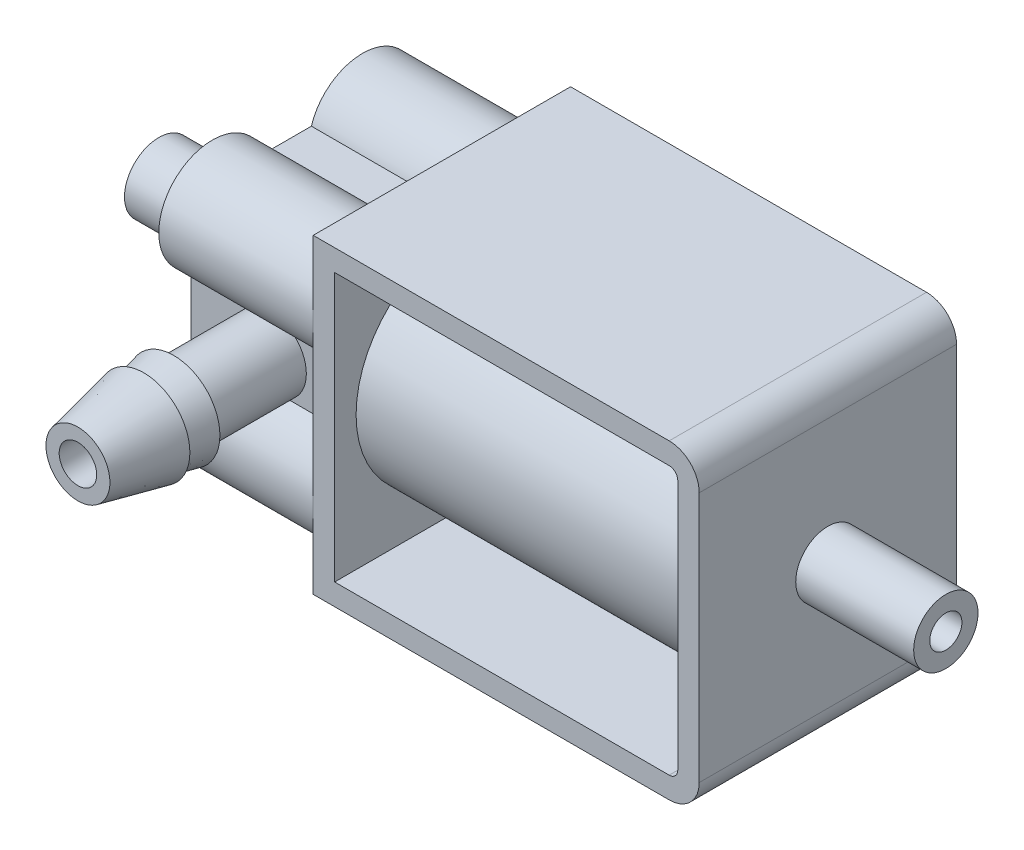
SolidWorks part; units mm, degrees
note: The reader was unsure of these and kept them because the rebuilt part matched: shared geometry of "Sketch4<6>".
ref_plane "Front Plane" through (0, 0, 0) normal (0, 0, 1) x (1, 0, 0)
ref_plane "Top Plane" through (0, 0, 0) normal (0, 1, 0) x (1, 0, 0)
ref_plane "Right Plane" through (0, 0, 0) normal (1, 0, 0) x (0, 0, -1)
sketch "Sketch1" plane through (0, 0, 0) normal (0, 0, 1) x (1, 0, 0)
  line L0 (9, -5.85) -> (9, 5.85)
  line L1 (-8, -6.25) -> (7.6, -6.25)
  line L2 (-8, -6.25) -> (-8, 6.25)
  line L3 (-8, 6.25) -> (7.6, 6.25)
  line L4 (8, -5.85) -> (8, 5.85)
  line L5 (-8, -6.25) -> (8, 6.25) construction
  line L6 (-8, 6.25) -> (8, -6.25) construction
  line L7 (-9, 7.25) -> (7.6, 7.25)
  line L8 (-9, -7.25) -> (-9, 7.25)
  line L9 (-9, -7.25) -> (7.6, -7.25)
  arc A0 (7.6, -6.25) -> (8, -5.85) centre (7.6, -5.85) ccw
  arc A1 (7.6, 6.25) -> (8, 5.85) centre (7.6, 5.85) cw
  arc A2 (7.6, 7.25) -> (9, 5.85) centre (7.6, 5.85) cw
  arc A3 (7.6, -7.25) -> (9, -5.85) centre (7.6, -5.85) ccw
  point P0 (0, 0)
  dimension "D3" = 0.4
  dimension "D1" = 18
  dimension "D2" = 14.5
  dimension "D4" = 1
extrude "Boss-Extrude1" add sketch "Sketch1" along normal blind 12
sketch "Sketch2" plane through (9, 0, 0) normal (1, 0, 0) x (0, 0, -1)
  line L0 (-12, -5.85) -> (0, 5.85) construction
  line L1 (-12, 5.85) -> (0, -5.85) construction
  line L2 (0, -5.85) -> (0, 5.85) construction
  circle A0 centre (-6, 0) radius 1.5
  circle A1 centre (-6, 0) radius 0.75
  point P12 (-6, 0)
  point P13 (0, 0)
  dimension "D1" = 3
  dimension "D2" = 1.5
extrude "Boss-Extrude2" add sketch "Sketch2" along normal blind 5.5
sketch "Sketch3" plane through (-8, 0, 0) normal (1, 0, 0) x (0, 0, -1)
  line L0 (-12, -6.25) -> (0, 6.25) construction
  line L1 (-12, 6.25) -> (0, -6.25) construction
  circle A0 centre (-6, 0) radius 5
  point P10 (-6, 0)
  point P11 (0, 0)
  dimension "D1" = 10
extrude "Boss-Extrude3" add sketch "Sketch3" along normal up to next
sketch "Sketch4" plane through (-9, 0, 0) normal (-1, 0, 0) x (0, 0, 1)
  line L0 (2.5, -3.75) -> (9.5, -3.75) construction
  line L1 (2.5, -3.75) -> (2.5, 3.75) construction
  line L2 (2.5, -3.75) -> (9.5, 3.75) construction
  line L3 (2.5, 3.75) -> (9.5, -3.75) construction
  line L4 (0, 7.25) -> (12, -7.25) construction
  line L5 (12, 7.25) -> (0, -7.25) construction
  line L6 (2.5, 3.75) -> (9.5, 3.75) construction
  line L7 (1.5, -4.5) -> (10.5, -4.5)
  line L8 (1.5, -4.5) -> (1.5, 4.5)
  line L9 (1.5, 4.5) -> (10.5, 4.5)
  line L10 (10.5, -4.5) -> (10.5, 4.5)
  line L11 (1.5, -4.5) -> (10.5, 4.5) construction
  line L12 (1.5, 4.5) -> (10.5, -4.5) construction
  line L13 (2.5, 3.75) -> (9.5, 3.75) construction
  circle A0 centre (2.5, -3.75) radius 2.5
  circle A1 centre (9.5, -3.75) radius 2.5
  circle A2 centre (9.5, 3.75) radius 2.5
  circle A3 centre (2.5, 3.75) radius 2.5
  circle A4 centre (2.5, 3.75) radius 1.85
  circle A5 centre (9.5, 3.75) radius 1.85
  circle A6 centre (9.5, -3.75) radius 1.85
  circle A7 centre (2.5, -3.75) radius 1.85
  circle A8 centre (2.5, 3.75) radius 1.1
  circle A9 centre (9.5, 3.75) radius 1.1
  circle A10 centre (9.5, -3.75) radius 1.1
  circle A11 centre (2.5, -3.75) radius 1.1
  point P2 (6, 0)
  point P4 (2.5, -3.75)
  point P20 (6, 0)
  point P21 (6, 0)
  dimension "D1" = 5
  dimension "D7" = 3.7
  dimension "D11" = 2.2
  dimension "D4" = 7
  dimension "D5" = 7.5
  dimension "D6" = 9
  dimension "D10" = 7
  dimension "D14" = 7
  dimension "D2" = 2
  dimension "D3" = 2
  dimension "D8" = 2
  dimension "D9" = 2
  dimension "D12" = 2
  dimension "D13" = 2
extrude "Boss-Extrude4" add sketch "Sketch4" along normal blind 7.2 separate body contours A5 L10 A2 L9 | L10 A5 L9 | L9 A5 L10 | A3 L8 A0 L7 A1 L10 A2 L9 | A4 L8 A3 L9 | A4 L9 A3 L8 | A7 L7 A0 L8 | A7 L8 A0 L7 | A6 L7 A1 L10 | A6 L10 A1 L7 | A5 L9 A2 L10
extrude "Boss-Extrude6" add sketch "Sketch4<6>" along normal blind 3.7 separate body contours A11 L7 A7 L8 | A11 L8 A7 L7 | A11 L8 L7 | A10 L7 A6 L10 | A10 L10 A6 L7 | A10 L7 L10 | A9 L9 L10 A5 | A9 L10 L9 | A9 L9 A5 L10 | A8 L8 A4 L9 | A8 L9 A4 L8 | A8 L9 L8
sketch "Sketch4<6>" plane through (-9, 0, 0) normal (-1, 0, 0) x (0, 0, 1) same geometry as "Sketch4"
combine bodies "Combine1" operation type add bodies to combine 104 106 109 108 107
sketch "Sketch5" plane through (-16.2, 0, 0) normal (-1, 0, 0) x (0, 0, 1)
  line L0 (6, 4.5) -> (6, -4.5) construction
  line L1 (4.8848, 4.5) -> (7.1152, 4.5) construction
  line L2 (4.8848, -4.5) -> (7.1152, -4.5) construction
  circle A0 centre (6, 0) radius 1.6
  circle A1 centre (6, 0) radius 0.57
  dimension "D1" = 3.2
  dimension "D2" = 1.14
extrude "Boss-Extrude7" add sketch "Sketch5" along normal blind 6
ref_plane "Plane1" through (0, 0, 15) normal (0, 0, 1) x (1, 0, 0)
sketch "Sketch6" plane through (0, 0, 15) normal (0, 0, 1) x (1, 0, 0)
  line L0 (-9, 1.4587) -> (-9, 6.25) construction
  line L1 (-16.2, -1.4587) -> (-9, -1.4587) construction
  line L2 (-16.2, 1.4587) -> (-9, 1.4587) construction
  line L3 (-16.2, -1.4587) -> (-9, -1.4587)
  line L4 (-16.2, 1.4587) -> (-9, 1.4587)
  line L5 (-12.5, 1.4587) -> (-12.5, -1.4587)
  circle A0 centre (-12.5, 0) radius 1.68
  circle A1 centre (-12.5, 0) radius 0.875
  point P11 (-12.5, 0.2784)
  dimension "D2" = 3.36
  dimension "D3" = 1.75
  dimension "D1" = 3.5
extrude "Boss-Extrude8" add sketch "Sketch6" against normal up to next contours A1 L5 L3 A0 L4 | A1 L5 L4 A0 L3 | L4 A0 | L3 A0
ref_plane "Plane2" through (-12.5, 0, 0) normal (-1, 0, 0) x (0, 0, 1)
sketch "Sketch8" plane through (-12.5, 0, 0) normal (-1, 0, 0) x (0, 0, 1)
  line L0 (15, -1.68) -> (15, 1.68) construction
  line L1 (15, -1.68) -> (15, 1.68)
  line L2 (15, 1.68) -> (15, 2.15)
  line L3 (15, 2.15) -> (16.4, 1.85)
  line L4 (15, 0) -> (19.47, 0) construction
  line L5 (16.4, 1.85) -> (16.4, 2.15)
  line L6 (16.4, 2.15) -> (19.47, 1.4921)
  line L7 (19.47, 1.4921) -> (19.47, 0)
  line L8 (19.47, 0.875) -> (15, 0.875)
  point P2 (15, 0)
  dimension "D1" = 2.15
  dimension "D2" = 1.85
  dimension "D3" = 1.4
  dimension "D4" = 4.47
  dimension "D5" = 0.875
revolve "Revolve1" add sketch "Sketch8" angle 360 about L4
